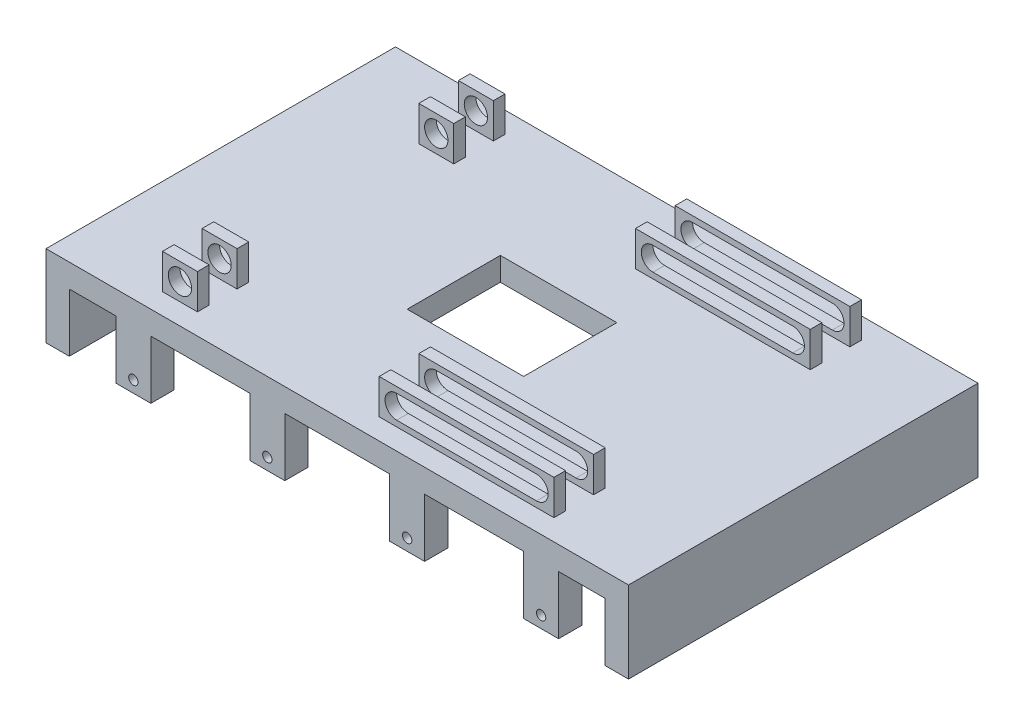
SolidWorks part; units mm, degrees
ref_plane "Front Plane" through (0, 0, 0) normal (0, 0, 1) x (1, 0, 0)
ref_plane "Top Plane" through (0, 0, 0) normal (0, 1, 0) x (1, 0, 0)
ref_plane "Right Plane" through (0, 0, 0) normal (1, 0, 0) x (0, 0, -1)
sketch "Sketch1" plane through (0, 0, 0) normal (0, 1, 0) x (1, 0, 0)
  line L0 (-125, -55) -> (125, -55) construction
  line L1 (-125, 75) -> (125, 75)
  line L2 (-125, 75) -> (-125, -75)
  line L3 (-125, -75) -> (125, -75)
  line L4 (125, 75) -> (125, -75)
  line L5 (-125, 75) -> (125, -75) construction
  line L6 (-125, -75) -> (125, 75) construction
  line L7 (84, -66) -> (9, -66)
  line L8 (-84, -61) -> (-69, -61)
  line L9 (-84, -44) -> (-69, -44)
  line L10 (-84, -44) -> (-84, -49)
  line L11 (-84, -49) -> (-69, -49)
  line L12 (-69, -44) -> (-69, -49)
  line L13 (-69, -66) -> (-69, -61)
  line L14 (-84, -66) -> (-69, -66)
  line L15 (-84, -66) -> (-84, -61)
  line L24 (84, -49) -> (9, -49)
  line L25 (84, -49) -> (84, -44)
  line L26 (84, -44) -> (9, -44)
  line L27 (9, -49) -> (9, -44)
  line L28 (84, -49) -> (9, -44) construction
  line L29 (84, -44) -> (9, -49) construction
  line L30 (9, -61) -> (9, -66)
  line L31 (84, -61) -> (9, -61)
  line L32 (84, -61) -> (84, -66)
  line L33 (-125, 0) -> (125, 0) construction
  line L34 (84, 44) -> (9, 44)
  line L35 (9, 49) -> (9, 44)
  line L36 (84, 49) -> (9, 49)
  line L37 (84, 49) -> (84, 44)
  line L38 (84, 61) -> (84, 66)
  line L39 (84, 61) -> (9, 61)
  line L40 (9, 61) -> (9, 66)
  line L41 (84, 66) -> (9, 66)
  line L42 (-84, 66) -> (-84, 61)
  line L43 (-84, 66) -> (-69, 66)
  line L44 (-69, 66) -> (-69, 61)
  line L45 (-84, 61) -> (-69, 61)
  line L46 (-84, 49) -> (-69, 49)
  line L47 (-69, 44) -> (-69, 49)
  line L48 (-84, 44) -> (-69, 44)
  line L49 (-84, 44) -> (-84, 49)
  point P0 (0, 0)
  point P8 (46.5, -46.5)
  point P25 (84, -63.5)
  dimension "D1" = 150
  dimension "D2" = 250
  dimension "D3" = 41
  dimension "D4" = 5
  dimension "D5" = 6
  dimension "D6" = 15
  dimension "D7" = 5
  dimension "D8" = 75
  dimension "D9" = 6
  dimension "D10" = 78
  dimension "D11" = 20
extrude "Boss-Extrude2" add sketch "Sketch1" along normal blind 10
extrude "Boss-Extrude3" add sketch "Sketch1<8>" along normal blind 25 contours L49 L48 L47 L46 | L42 L45 L44 L43 | L38 L41 L40 L39 | L37 L36 L35 L34 | L9 L12 L11 L10 | L8 L13 L14 L15 | L24 L27 L26 L25 | L31 L30 L7 L32 region at (46.5, 0, -46.5) region at (46.5, 0, -63.5) region at (-76.5, 0, -63.5) region at (-76.5, 0, -46.5)
sketch "Sketch1<8>" plane through (0, 0, 0) normal (0, 1, 0) x (1, 0, 0) same geometry as "Sketch1"
sketch "Sketch5" plane through (0, 0, 0) normal (0, -1, 0) x (1, 0, 0)
  line L0 (125, -75) -> (-125, -75) construction
  line L1 (-125, 75) -> (-115, 75)
  line L2 (-125, 75) -> (-125, -75)
  line L3 (-125, -75) -> (-90, -75)
  line L4 (-115, 65) -> (-115, -65)
  line L6 (125, 75) -> (115, 75)
  line L7 (125, 75) -> (125, -75)
  line L8 (125, -75) -> (90, -75)
  line L9 (115, 65) -> (115, -65)
  line L10 (-115, 75) -> (115, 75)
  line L12 (-115, 65) -> (115, 65)
  line L14 (90, -75) -> (-90, -75)
  line L16 (115, -65) -> (-115, -65)
  point P16 (0, 0)
  dimension "D1" = 10
  dimension "D2" = 10
  dimension "D3" = 10
  dimension "D4" = 10
extrude "Boss-Extrude4" add sketch "Sketch5" along normal blind 25
sketch "Sketch7" plane through (0, 0, 44) normal (0, 0, -1) x (-1, 0, 0)
  line L0 (69, 25) -> (84, 10) construction
  line L1 (84, 25) -> (69, 10) construction
  circle A0 centre (76.5, 17.5) radius 5
  dimension "D1" = 10
extrude "Cut-Extrude2" cut sketch "Sketch7" against normal through all both and the other way through all
sketch "Sketch8" plane through (0, 0, 66) normal (0, 0, 1) x (1, 0, 0)
  line L0 (16.5, 17.5) -> (76.5, 17.5) construction
  line L1 (16.5, 22.5) -> (76.5, 22.5)
  line L2 (16.5, 12.5) -> (76.5, 12.5)
  line L3 (84, 25) -> (9, 25) construction
  line L4 (84, 25) -> (84, 10) construction
  line L5 (9, 25) -> (9, 10) construction
  arc A0 (16.5, 22.5) -> (16.5, 12.5) centre (16.5, 17.5) ccw
  arc A1 (76.5, 12.5) -> (76.5, 22.5) centre (76.5, 17.5) ccw
  point P2 (46.5, 17.5)
  dimension "D2" = 5
  dimension "D1" = 7.5
  dimension "D3" = 7.5
  dimension "D4" = 7.5
extrude "Cut-Extrude3" cut sketch "Sketch8" against normal through all
sketch "Sketch9" plane through (0, 10, 0) normal (0, 1, 0) x (1, 0, 0)
  line L0 (125, 75) -> (-125, 75) construction
  line L1 (-25, 20) -> (25, 20)
  line L2 (-25, 20) -> (-25, -20)
  line L3 (-25, -20) -> (25, -20)
  line L4 (25, 20) -> (25, -20)
  line L5 (-25, 20) -> (25, -20) construction
  line L6 (-25, -20) -> (25, 20) construction
  line L7 (-125, 75) -> (-125, -75) construction
  point P0 (0, 0)
  point P7 (0, 75)
  point P10 (-125, 0)
  dimension "D1" = 50
  dimension "D2" = 40
extrude "Cut-Extrude4" cut sketch "Sketch9" against normal blind 10 contours L4 L1 L2 L3 region at (0, 10, 0)
sketch "Sketch10" plane through (0, 0, 75) normal (0, 0, 1) x (1, 0, 0)
  line L0 (-80, -25) -> (-37.5, -25)
  line L6 (-37.5, -25) -> (-37.5, 0)
  line L7 (125, -25) -> (-125, -25) construction
  line L8 (-115, -25) -> (-95, -25)
  line L13 (-22.5, 0) -> (-22.5, -25)
  line L15 (-115, -25) -> (-115, 0)
  line L27 (-115, 0) -> (-95, 0)
  line L28 (-95, -25) -> (-95, 0)
  line L29 (-125, 10) -> (-125, -25) construction
  line L30 (-125, 10) -> (125, 10) construction
  line L31 (0, 10) -> (0, 0) construction
  line L32 (-80, 0) -> (-95, -25) construction
  line L35 (80, 0) -> (37.5, 0)
  line L36 (-80, -25) -> (-80, 0)
  line L37 (-95, 0) -> (-80, -25) construction
  line L38 (115, 0) -> (95, 0)
  line L39 (95, -25) -> (95, 0)
  line L40 (115, -25) -> (95, -25)
  line L41 (115, -25) -> (115, 0)
  line L42 (80, -25) -> (80, 0)
  line L43 (-22.5, -25) -> (22.5, -25)
  line L44 (22.5, -25) -> (22.5, 0)
  line L45 (37.5, 0) -> (37.5, -25)
  line L46 (37.5, -25) -> (80, -25)
  line L47 (-22.5, 0) -> (-37.5, 0) construction
  line L48 (-37.5, 0) -> (-80, 0)
  line L49 (37.5, 0) -> (22.5, 0) construction
  line L50 (22.5, 0) -> (-22.5, 0)
  circle A2 centre (-87.5, -20) radius 2
  circle A3 centre (87.5, -20) radius 2
  circle A4 centre (-30, -20) radius 2
  circle A5 centre (30, -20) radius 2
  point P19 (-87.5, -12.5)
  point P39 (-30, 0)
  point P40 (30, 0)
  dimension "D6" = 5
  dimension "D7" = 10
  dimension "D3" = 15
  dimension "D5" = 4
  dimension "D12" = 4
  dimension "D13" = 4
  dimension "D1" = 10
  dimension "D2" = 10
  dimension "D4" = 15
  dimension "D8" = 15
  dimension "D9" = 20
  dimension "D10" = 42.5
  dimension "D11" = 45
extrude "Cut-Extrude5" cut sketch "Sketch10" against normal through all both and the other way through all
